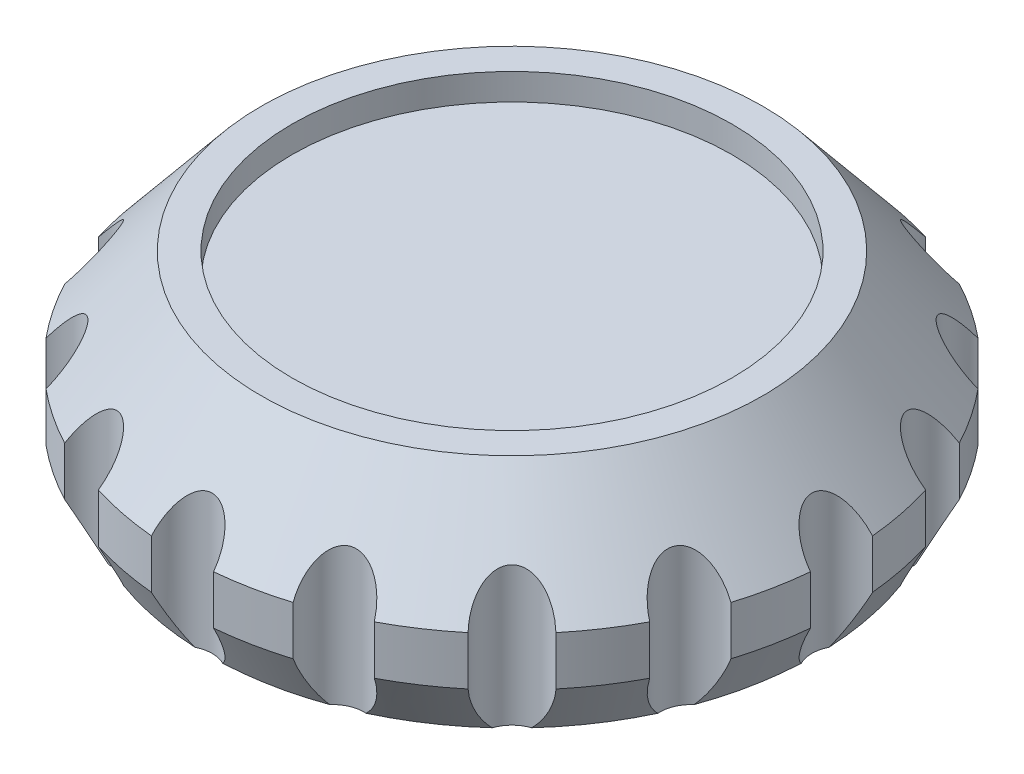
SolidWorks part; units mm, degrees
ref_plane "Front Plane" through (0, 0, 0) normal (0, 0, 1) x (1, 0, 0)
ref_plane "Top Plane" through (0, 0, 0) normal (0, 1, 0) x (1, 0, 0)
ref_plane "Right Plane" through (0, 0, 0) normal (1, 0, 0) x (0, 0, -1)
sketch "Sketch1" plane through (0, 0, 0) normal (0, 1, 0) x (1, 0, 0)
  circle A0 centre (0, 0) radius 63.5
  dimension "D1" = 127
extrude "Boss-Extrude1" add sketch "Sketch1" along normal blind 38.1
sketch "Sketch7" plane through (0, 0, 0) normal (0, -1, 0) x (1, 0, 0)
  line L0 (-46.0328, 0) -> (0, 46.0328) construction
  line L1 (0, 46.0328) -> (46.0328, 0) construction
  line L2 (46.0328, 0) -> (0, -46.0328) construction
  line L3 (0, -46.0328) -> (-46.0328, 0) construction
  line L4 (0, 46.0328) -> (0, -46.0328) construction
  line L5 (46.0328, 0) -> (-46.0328, 0) construction
  circle A0 centre (0, 46.0328) radius 1.9844
  circle A1 centre (46.0328, 0) radius 1.9844
  circle A2 centre (0, -46.0328) radius 1.9844
  circle A3 centre (-46.0328, 0) radius 1.9844
extrude "Cut-Extrude4" cut sketch "Sketch7" against normal blind 2.54
sketch "Sketch3" plane through (0, 0, 0) normal (1, 0, 0) x (0, 0, -1)
  line L0 (58.213, 0) -> (63.5, 10.026)
  line L1 (-63.5, 0) -> (63.5, 0) construction
  line L2 (63.5, 0) -> (63.5, 38.1) construction
  line L4 (63.5, 19.3945) -> (48.1239, 38.1)
  line L5 (63.5, 38.1) -> (-63.5, 38.1) construction
  line L6 (48.1239, 38.1) -> (63.5, 38.1)
  line L7 (63.5, 38.1) -> (63.5, 19.3945)
  line L8 (63.5, 0) -> (58.213, 0)
  line L9 (0, 0) -> (0, 50000) construction
  line L10 (63.5, 10.026) -> (63.5, 0)
revolve "Cut-Revolve1" cut sketch "Sketch3" angle 360 about L9
sketch "Sketch5" plane through (0, 0, 0) normal (0, 1, 0) x (1, 0, 0)
  circle A0 centre (0, 63.5) radius 5.9672
  circle A1 centre (0, 0) radius 63.5 construction
  circle A2 centre (24.3004, 58.6664) radius 5.9672
  circle A3 centre (44.9013, 44.9013) radius 5.9672
  circle A4 centre (58.6664, 24.3004) radius 5.9672
  circle A5 centre (63.5, 0) radius 5.9672
  circle A6 centre (58.6664, -24.3004) radius 5.9672
  circle A7 centre (44.9013, -44.9013) radius 5.9672
  circle A8 centre (24.3004, -58.6664) radius 5.9672
  circle A9 centre (0, -63.5) radius 5.9672
  circle A10 centre (-24.3004, -58.6664) radius 5.9672
  circle A11 centre (-44.9013, -44.9013) radius 5.9672
  circle A12 centre (-58.6664, -24.3004) radius 5.9672
  circle A13 centre (-63.5, 0) radius 5.9672
  circle A14 centre (-58.6664, 24.3004) radius 5.9672
  circle A15 centre (-44.9013, 44.9013) radius 5.9672
  circle A16 centre (-24.3004, 58.6664) radius 5.9672
  dimension "D1" = 16
extrude "Cut-Extrude2" cut sketch "Sketch5" along normal through all
sketch "Sketch6" plane through (0, 38.1, 0) normal (0, 1, 0) x (1, 0, 0)
  circle A0 centre (0, 0) radius 42.2001
extrude "Cut-Extrude3" cut sketch "Sketch6" against normal blind 5.08
